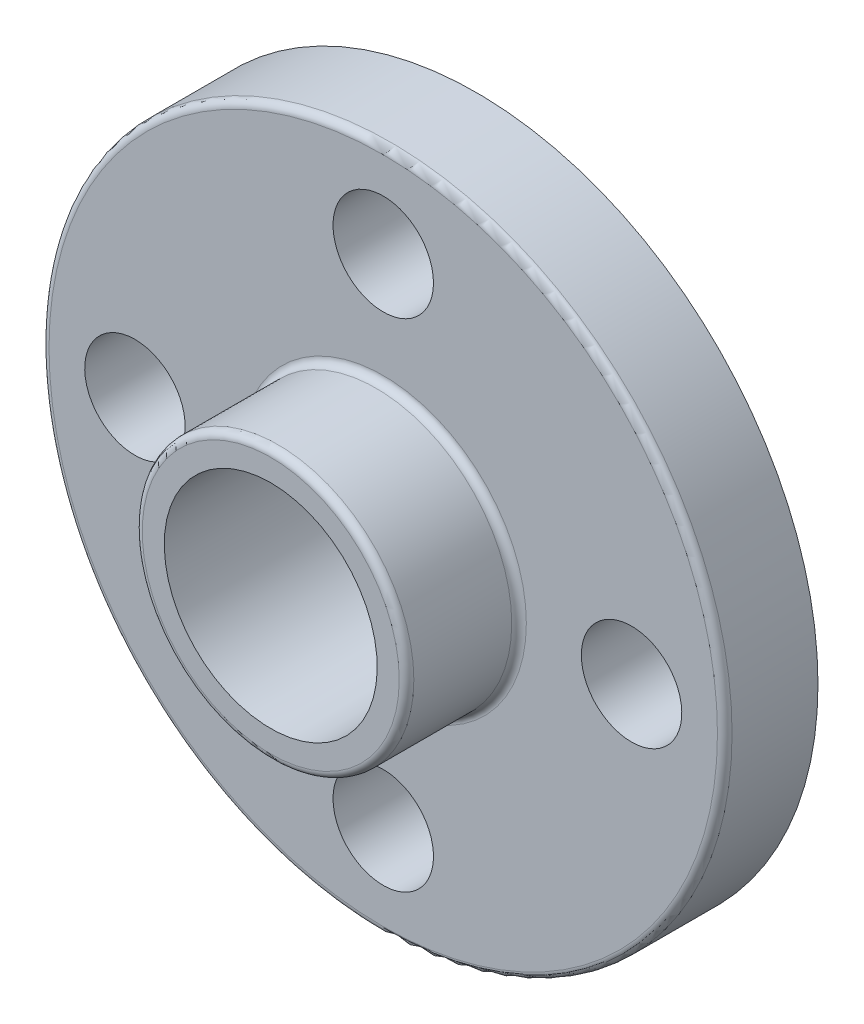
SolidWorks part; units mm, degrees
ref_plane "Front Plane" through (0, 0, 0) normal (0, 0, 1) x (1, 0, 0)
ref_plane "Top Plane" through (0, 0, 0) normal (0, 1, 0) x (1, 0, 0)
ref_plane "Right Plane" through (0, 0, 0) normal (1, 0, 0) x (0, 0, -1)
sketch "Sketch0" plane through (0, 0, 0) normal (1, 0, 0) x (0, 0, -1)
  line L0 (0, 0) -> (-32.512, 0) construction
  point P3 (-14.732, 0)
  point P4 (-4.064, 0)
  dimension "Q" = 14.732
  dimension "C" = 32.512
  dimension "N" = 4.064
sketch "Sketch1" plane through (0, 0, 0) normal (0, 0, 1) x (1, 0, 0)
  circle A0 centre (0, 0) radius 53.975
  circle A1 centre (0, 0) radius 16.8275 construction
  circle A2 centre (0, 0) radius 39.243 construction
  circle A3 centre (0, 39.243) radius 7.9375 construction
  circle A4 centre (0, 0) radius 21.463 construction
  circle A5 centre (0, 0) radius 12.1539 construction
  circle A6 centre (0, 0) radius 16.637 construction
  point P9 (0, 16.8275)
  point P10 (0, 16.637)
  point P11 (0, 12.1539)
  dimension "A" = 107.95
  dimension "B" = 78.486
  dimension "Bolt Hole Size" = 15.875
  dimension "Pipe OD A" = 33.655
  dimension "Hub OD" = 42.926
  dimension "Pipe ID" = 24.3078
  dimension "Pipe OD B" = 33.274
extrude "Extrude1" add sketch "Sketch1" along normal up to vertex (14.732 mm away) up to point (0, 0, 14.732)
sketch "Sketch2" plane through (0, 0, 14.732) normal (0, 0, 1) x (1, 0, 0)
  circle A0 centre (0, 0) radius 21.463 construction
  circle A1 centre (0, 0) radius 21.463
extrude "Extrude2" add sketch "Sketch2" along normal up to vertex (17.78 mm away) up to point (0, 0, 32.512)
sketch "Sketch3" plane through (0, 0, 14.732) normal (0, 0, 1) x (1, 0, 0)
  circle A0 centre (0, 39.243) radius 7.9375 construction
  circle A1 centre (0, 39.243) radius 7.9375
extrude "Extrude3" cut sketch "Sketch3" against normal through all
ref_axis "Axis1" through (0, 0, -1.6256) along (0, 0, 1)
pattern_circular "CirPattern1" count 4 over 360 about axis through (0, 0, -1.6256) along (0, 0, 1) of "Extrude3"
fillet "Fillet1" radius 1.1545 3 edges at (21.463, 0, 32.512) (21.463, 0, 14.732) (53.975, 0, 14.732) tangent propagation no
sketch "Sketch4" plane through (0, 0, 63.5) normal (1, 0, 0) x (0, 0, -1)
  line L0 (30.988, 16.8275) -> (59.436, 16.637)
  line L1 (59.436, 16.637) -> (59.436, 12.1539)
  line L2 (59.436, 12.1539) -> (63.5, 12.1539)
  line L3 (63.5, 12.1539) -> (63.5, 0)
  line L4 (63.5, 0) -> (30.988, 0)
  line L5 (30.988, 0) -> (30.988, 16.8275)
  line L6 (63.5, 39.243) -> (63.5, -39.243) construction
  line L7 (59.436, 0) -> (59.436, 12.1539) construction
  line L8 (30.988, 16.8275) -> (63.5, 16.8275) construction
  line L12 (63.5, 16.637) -> (59.436, 16.637) construction
revolve "Cut-Revolve1" cut sketch "Sketch4" angle 360 about L4
